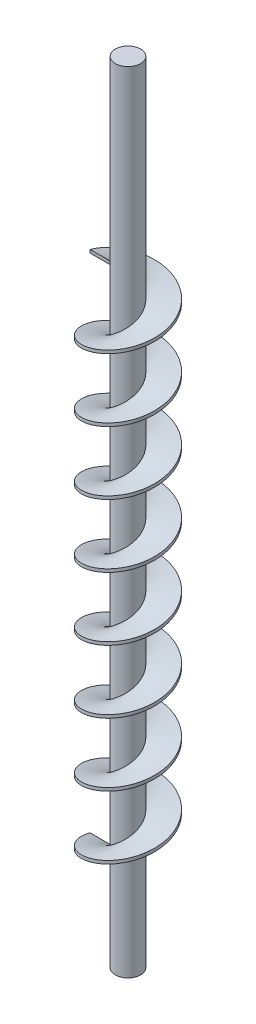
SolidWorks part; units mm, degrees
ref_plane "Front Plane" through (0, 0, 0) normal (0, 0, 1) x (1, 0, 0)
ref_plane "Top Plane" through (0, 0, 0) normal (0, 1, 0) x (1, 0, 0)
ref_plane "Right Plane" through (0, 0, 0) normal (1, 0, 0) x (0, 0, -1)
sketch "Sketch1" plane through (0, 0, 0) normal (0, 1, 0) x (1, 0, 0)
  circle A0 centre (0, 0) radius 4
  dimension "D1" = 8
extrude "Boss-Extrude1" add sketch "Sketch1" along normal blind 220
sketch "Sketch3" plane through (0, 0, 0) normal (0, -1, 0) x (1, 0, 0)
  circle A0 centre (0, 0) radius 10
curve "Helix/Spiral1" pitch 20 height 160 radius 10 centre (0, 0, 0) axis (0, 1, 0) start towards (0, 0, -1)
sketch "Sketch4" plane through (0, 0, 0) normal (0, 0, 1) x (1, 0, 0)
  line L0 (-4, 0) -> (-12, 0)
  line L1 (-12, 0) -> (-12, 1)
  line L2 (-12, 1) -> (-4, 1)
  line L3 (-4, 220) -> (-4, 0) construction
  line L4 (-4, 1) -> (-4, 0)
  dimension "D1" = 12
  dimension "D2" = 1
sweep "Sweep1" add profiles "Sketch4" path "Helix/Spiral1"
sketch "Sketch6" plane through (0, 0, 0) normal (0, -1, 0) x (1, 0, 0)
  circle A1 centre (0, 0) radius 4
  circle A2 centre (0, 0) radius 4
  dimension "D1" = 0
extrude "Boss-Extrude2" add sketch "Sketch6" along normal blind 30
